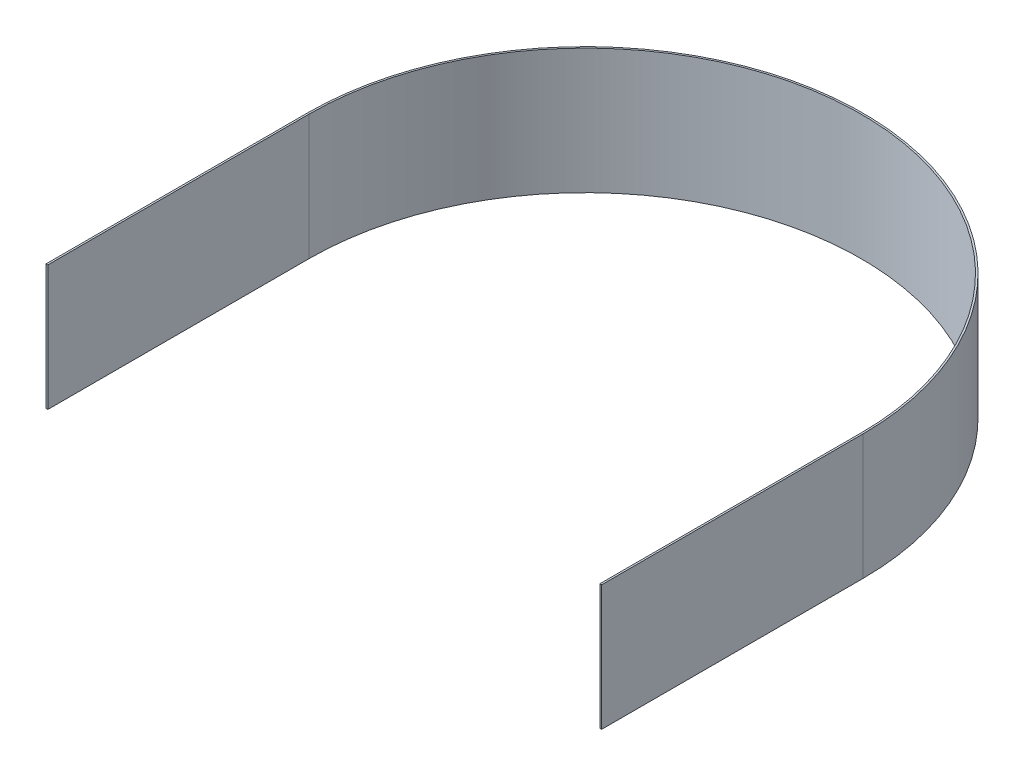
SolidWorks part; units mm, degrees
ref_plane "Front Plane" through (0, 0, 0) normal (0, 0, 1) x (1, 0, 0)
ref_plane "Top Plane" through (0, 0, 0) normal (0, 1, 0) x (1, 0, 0)
ref_plane "Right Plane" through (0, 0, 0) normal (1, 0, 0) x (0, 0, -1)
sketch "Sketch1" plane through (0, 0, 0) normal (0, 1, 0) x (1, 0, 0)
  line L0 (-154.3284, -146.0327) -> (-155.3284, -146.0327)
  line L1 (-155.3284, -146.0327) -> (-155.3284, 0)
  line L2 (-154.3284, -146.0327) -> (-154.3284, 0)
  line L3 (154.3284, -146.0763) -> (155.3284, -146.0763)
  line L4 (155.3284, -146.0763) -> (155.3284, 0)
  line L5 (154.3284, -146.0763) -> (154.3284, 0)
  line L6 (0, 0) -> (50000, 0) construction
  line L9 (0, 0) -> (0, 50000) construction
  arc A0 (-154.3284, 0) -> (154.3284, 0) centre (0, 0) cw
  arc A1 (-155.3284, 0) -> (155.3284, 0) centre (0, 0) cw
  dimension "D1" = 1
extrude "Boss-Extrude1" add sketch "Sketch1" along normal blind 70
ref_plane "Plane1" through (0, 0, 136.0327) normal (0, 0, 1) x (1, 0, 0)
ref_plane "Plane2" through (0, 10, 0) normal (0, -1, 0) x (-1, 0, 0)
ref_axis "Axis1" through (-155.3784, 10, 136.0327) along (1, 0, 0)
